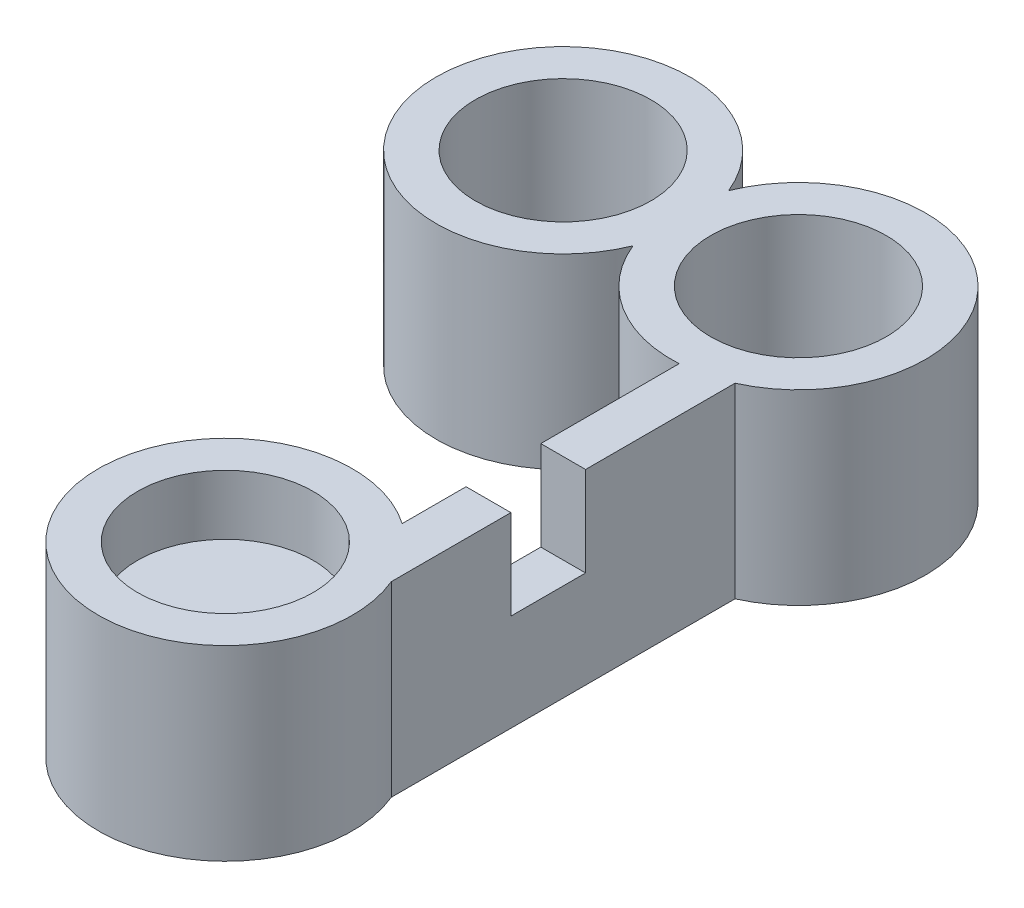
SolidWorks part; units mm, degrees
ref_plane "Front Plane" through (0, 0, 0) normal (0, 0, 1) x (1, 0, 0)
ref_plane "Top Plane" through (0, 0, 0) normal (0, 1, 0) x (1, 0, 0)
ref_plane "Right Plane" through (0, 0, 0) normal (1, 0, 0) x (0, 0, -1)
sketch "Sketch1" plane through (0, 0, 0) normal (0, 1, 0) x (1, 0, 0)
  line L0 (0, 24.892) -> (0, 12.192) construction
  line L1 (0, 0) -> (-15.621, 0) construction
  line L2 (0, 0) -> (0, 24.892) construction
  line L3 (0, 24.892) -> (-15.621, 24.892) construction
  line L4 (-15.621, 0) -> (-15.621, 24.892) construction
  line L5 (-2.032, 17.147) -> (-2.032, 5.463)
  line L6 (-3.556, 16.7715) -> (-3.556, 7.3552)
  arc A0 (-7.5525, 20.3678) -> (-7.5525, 21.7962) centre (-3.81, 21.082) ccw construction
  arc A1 (-8.0685, 21.7962) -> (-8.0685, 20.3678) centre (-11.811, 21.082) ccw construction
  circle A2 centre (-11.811, 21.082) radius 2.9845
  circle A3 centre (-3.81, 21.082) radius 2.9845
  arc A5 (-7.8105, 22.7072) -> (-7.8105, 19.4568) centre (-11.811, 21.082) ccw
  arc A6 (-2.032, 17.147) -> (-7.8105, 22.7072) centre (-3.81, 21.082) ccw
  circle A7 centre (-6.0211, 3.81) radius 3.81 construction
  circle A8 centre (-6.0211, 3.81) radius 2.9845
  arc A9 (-3.556, 7.3552) -> (-2.032, 5.463) centre (-6.0211, 3.81) ccw
  circle A10 centre (-3.81, 21.082) radius 4.318 construction
  circle A11 centre (-11.811, 21.082) radius 4.318 construction
  circle A12 centre (-3.81, 21.082) radius 3.81 construction
  circle A13 centre (-11.811, 21.082) radius 3.81 construction
  arc A14 (-7.8105, 19.4568) -> (-3.556, 16.7715) centre (-3.81, 21.082) ccw
  dimension "D3" = 7.62
  dimension "D4" = 5.969
  dimension "D6" = 7.62
  dimension "D1" = 24.892
  dimension "D2" = 15.621
  dimension "D7" = 12.7
  dimension "D8" = 11.684
  dimension "D9" = 1.524
  dimension "D10" = 2.032
  dimension "D5" = 0.508
extrude "Boss-Extrude1" add sketch "Sketch1" along normal blind 6.35
sketch "Sketch2" plane through (-2.032, 0, 0) normal (1, 0, 0) x (0, 0, -1)
  line L1 (9.527, 6.35) -> (12.067, 6.35)
  line L2 (9.527, 6.35) -> (9.527, 3.302)
  line L3 (9.527, 3.302) -> (12.067, 3.302)
  line L4 (5.463, 0) -> (17.147, 0)
  line L5 (17.147, 0) -> (17.147, 6.35)
  line L6 (17.147, 6.35) -> (5.463, 6.35)
  line L7 (5.463, 6.35) -> (5.463, 0)
  line L8 (5.463, 0) -> (17.147, 0) construction
  line L9 (17.147, 0) -> (17.147, 6.35) construction
  line L10 (17.147, 6.35) -> (5.463, 6.35) construction
  line L11 (5.463, 6.35) -> (5.463, 0) construction
  line L12 (12.067, 6.35) -> (12.067, 3.302)
  dimension "D2" = 3.048
  dimension "D3" = 2.54
  dimension "D4" = 5.08
  dimension "D1" = 0
extrude "Cut-Extrude1" cut sketch "Sketch2" against normal blind 6.35
sketch "Sketch3" plane through (0, 0, 0) normal (0, 1, 0) x (1, 0, 0)
  circle A0 centre (-6.0211, 3.81) radius 2.9845
extrude "Boss-Extrude2" add sketch "Sketch3" along normal blind 4.318
